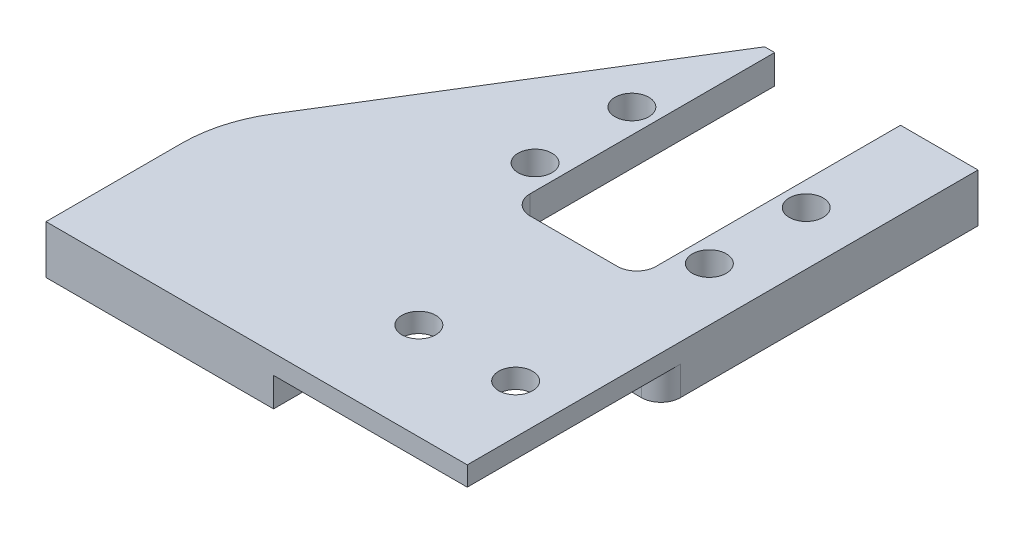
SolidWorks part; units mm, degrees
ref_plane "前视基准面" through (0, 0, 0) normal (0, 0, 1) x (1, 0, 0)
ref_plane "上视基准面" through (0, 0, 0) normal (0, 1, 0) x (1, 0, 0)
ref_plane "右视基准面" through (0, 0, 0) normal (1, 0, 0) x (0, 0, -1)
sketch "草图1" plane through (0, 0, 0) normal (0, 1, 0) x (1, 0, 0)
  line L1 (-17.5, -27.5) -> (17.5, -27.5)
  line L2 (-17.5, -27.5) -> (-17.5, 27.5)
  line L3 (-17.5, 27.5) -> (17.5, 27.5)
  line L4 (17.5, -27.5) -> (17.5, 27.5)
  line L5 (-17.5, -27.5) -> (17.5, 27.5) construction
  line L6 (-17.5, 27.5) -> (17.5, -27.5) construction
  point P0 (0, 0)
  dimension "D1" = 55
  dimension "D2" = 35
extrude "凸台-拉伸1" add sketch "草图1" along normal blind 1
sketch "草图2" plane through (0, 1, 0) normal (0, 1, 0) x (1, 0, 0)
  line L0 (-105.917, 0) -> (-62.25, 0) construction
  line L1 (106.75, 2.25) -> (121.75, 2.25)
  line L2 (-31.4474, 57.1013) -> (151.75, 26.6691)
  line L4 (124.0586, 2.6571) -> (154.0586, 13.5762)
  line L5 (-60.1618, 23.6059) -> (-42.6093, 52.0296)
  line L6 (121.75, 2.25) -> (121.75, 9) construction
  line L7 (121.75, -2.25) -> (121.75, -9) construction
  line L8 (-60.1618, -23.6059) -> (-42.6093, -52.0296)
  line L9 (124.0586, -2.6571) -> (154.0586, -13.5762)
  line L10 (121.75, -9) -> (128.5, -9)
  line L11 (-31.4474, -57.1013) -> (151.75, -26.6691)
  line L12 (106.75, -2.25) -> (121.75, -2.25)
  line L13 (-62.25, 16.25) -> (-62.25, -16.25)
  line L14 (106.75, 2.25) -> (106.75, -2.25)
  line L15 (106.75, 0) -> (124.0666, 0) construction
  arc A0 (-60.1618, 23.6059) -> (-62.25, 16.25) centre (-48.25, 16.25) ccw
  arc A1 (-31.4474, 57.1013) -> (-42.6093, 52.0296) centre (-33.25, 46.25) ccw
  arc A2 (121.75, 2.25) -> (124.0586, 2.6571) centre (121.75, 9) ccw
  arc A3 (154.0586, 13.5762) -> (151.75, 26.6691) centre (151.75, 19.9191) ccw
  arc A4 (154.0586, -13.5762) -> (151.75, -26.6691) centre (151.75, -19.9191) cw
  arc A5 (121.75, -2.25) -> (128.5, -9) centre (121.75, -9) cw
  arc A6 (-31.4474, -57.1013) -> (-42.6093, -52.0296) centre (-33.25, -46.25) cw
  arc A7 (-60.1618, -23.6059) -> (-62.25, -16.25) centre (-48.25, -16.25) cw
  line M10 (17.5, -27.5) -> (17.5, 27.5)
  line M11 (17.5, 27.5) -> (-17.5, 27.5)
  line M12 (-17.5, 27.5) -> (-17.5, -27.5)
  line M13 (-17.5, -27.5) -> (17.5, -27.5)
  dimension "D2" = 28
  dimension "D3" = 48.25
  dimension "D4" = 22
  dimension "D5" = 15
  dimension "D7" = 13.5
  dimension "D10" = 13.5
  dimension "D11" = 30
  dimension "D1" = 2.25
  dimension "D8" = 20
  dimension "D9" = 30
  dimension "D12" = 15
extrude "凸台-拉伸2" add sketch "草图2" along normal blind 3 contours A7 L8 A6 L11 A4 L9 A5 L12 L14 L1 A2 L4 A3 L2 A1 L5 A0 L13 | M13 M10 M11 M12 region at (37.3678, 1, 0) region at (0, 1, 0)
sketch "草图3" plane through (0, 4, 0) normal (0, 1, 0) x (1, 0, 0)
  circle A0 centre (-48.25, 16.25) radius 5
  circle A1 centre (-48.25, -16.25) radius 5
  circle A2 centre (-33.25, 46.25) radius 6.6982
  circle A3 centre (151.75, 19.9191) radius 2.5794
  circle A4 centre (121.75, 9) radius 2.5794
  circle A5 centre (121.75, -9) radius 2.5794
  circle A6 centre (151.75, -19.9191) radius 2.5794
  circle A7 centre (-33.25, -46.25) radius 6.6982
  dimension "D1" = 10
extrude "切除-拉伸1" cut sketch "草图3" against normal through all contours A0 | A1 region at (-48.25, 4, -16.25)
sketch "草图4" plane through (0, 4, 0) normal (0, 1, 0) x (1, 0, 0)
  circle A0 centre (-33.25, 46.25) radius 4
  circle A1 centre (-33.25, -46.25) radius 4
  dimension "D1" = 8
  dimension "D2" = 8
extrude "切除-拉伸2" cut sketch "草图4" against normal blind 2
sketch "草图5" plane through (0, 4, 0) normal (0, 1, 0) x (1, 0, 0)
  circle A0 centre (121.75, 9) radius 2
  circle A1 centre (121.75, -9) radius 2
  circle A2 centre (151.75, 19.9191) radius 2
  circle A3 centre (151.75, -19.9191) radius 2
  dimension "D1" = 4
extrude "切除-拉伸3" cut sketch "草图5" against normal blind 2
sketch "草图8" plane through (0, 1, 0) normal (0, -1, 0) x (1, 0, 0)
  line L1 (-39.75, -26.25) -> (-26.75, -26.25)
  line L2 (-39.75, -26.25) -> (-39.75, -66.25)
  line L3 (-39.75, -66.25) -> (-26.75, -66.25)
  line L4 (-26.75, -26.25) -> (-26.75, -66.25)
  line L5 (-39.75, -26.25) -> (-26.75, -66.25) construction
  line L6 (-39.75, -66.25) -> (-26.75, -26.25) construction
  line L16 (124.0586, 2.6571) -> (154.0586, 13.5762)
  line L17 (151.75, 26.6691) -> (-31.4474, 57.1013)
  line L18 (-42.6093, 52.0296) -> (-60.1618, 23.6059)
  line L19 (-62.25, 16.25) -> (-62.25, -16.25)
  line L20 (-60.1618, -23.6059) -> (-42.6093, -52.0296)
  line L21 (-31.4474, -57.1013) -> (151.75, -26.6691)
  line L22 (154.0586, -13.5762) -> (124.0586, -2.6571)
  line L23 (121.75, -2.25) -> (106.75, -2.25)
  line L24 (106.75, -2.25) -> (106.75, 2.25)
  line L25 (106.75, 2.25) -> (121.75, 2.25)
  line L26 (124.0586, 2.6571) -> (154.0586, 13.5762)
  line L27 (151.75, 26.6691) -> (-31.4474, 57.1013)
  line L28 (-42.6093, 52.0296) -> (-60.1618, 23.6059)
  line L31 (-31.4474, -57.1013) -> (151.75, -26.6691)
  line L32 (154.0586, -13.5762) -> (124.0586, -2.6571)
  line L33 (121.75, -2.25) -> (106.75, -2.25)
  line L34 (106.75, -2.25) -> (106.75, 2.25)
  line L35 (106.75, 2.25) -> (121.75, 2.25)
  arc A8 (154.0586, 13.5762) -> (151.75, 26.6691) centre (151.75, 19.9191) ccw
  arc A9 (-31.4474, 57.1013) -> (-42.6093, 52.0296) centre (-33.25, 46.25) ccw
  arc A10 (-60.1618, 23.6059) -> (-62.25, 16.25) centre (-48.25, 16.25) ccw
  arc A11 (-62.25, -16.25) -> (-60.1618, -23.6059) centre (-48.25, -16.25) ccw
  arc A12 (-42.6093, -52.0296) -> (-31.4474, -57.1013) centre (-33.25, -46.25) ccw
  arc A13 (151.75, -26.6691) -> (154.0586, -13.5762) centre (151.75, -19.9191) ccw
  arc A14 (124.0586, -2.6571) -> (121.75, -2.25) centre (121.75, -9) ccw
  arc A15 (121.75, 2.25) -> (124.0586, 2.6571) centre (121.75, 9) ccw
  arc A16 (154.0586, 13.5762) -> (151.75, 26.6691) centre (151.75, 19.9191) ccw
  arc A17 (-31.4474, 57.1013) -> (-42.6093, 52.0296) centre (-33.25, 46.25) ccw
  arc A18 (-60.1618, 23.6059) -> (-62.25, 16.25) centre (-48.25, 16.25) ccw
  arc A19 (-62.25, -16.25) -> (-60.1618, -23.6059) centre (-48.25, -16.25) ccw
  arc A20 (-42.6093, -52.0296) -> (-31.4474, -57.1013) centre (-33.25, -46.25) ccw
  arc A21 (151.75, -26.6691) -> (154.0586, -13.5762) centre (151.75, -19.9191) ccw
  arc A22 (124.0586, -2.6571) -> (121.75, -2.25) centre (121.75, -9) ccw
  arc A23 (121.75, 2.25) -> (124.0586, 2.6571) centre (121.75, 9) ccw
  point P0 (-33.25, -46.25)
  arc M32 (-42.6093, -52.0296) -> (-31.4474, -57.1013) centre (-33.25, -46.25) ccw
  line M33 (-31.4474, -57.1013) -> (151.75, -26.6691)
  dimension "D1" = 13
  dimension "D2" = 40
  dimension "D3" = 0
extrude "凸台-拉伸3" add sketch "草图8" along normal blind 7 contours L4 L1 L2 M32 M33 region at (-33.2258, 1, -41.4837)
mirror "镜向1" about plane through (0, 0, 0) normal (0, 0, 1) of "凸台-拉伸3"
sketch "草图9" plane through (0, -6, 0) normal (0, -1, 0) x (1, 0, 0)
  line L0 (-39.75, -26.25) -> (-26.75, -26.25) construction
  line L2 (-38.25, -53.75) -> (-38.25, -27.75)
  line L3 (-38.25, -27.75) -> (-28.25, -27.75)
  line L4 (-28.25, -53.75) -> (-28.25, -27.75)
  line L5 (-35.5448, -54.7408) -> (-28.25, -27.75) construction
  line L6 (-38.25, -27.75) -> (-31.223, -53.75) construction
  line L8 (-28.25, -53.75) -> (-38.25, -53.75)
  point P0 (-33.25, -46.25)
  dimension "D1" = 10
  dimension "D2" = 1.5
  dimension "D3" = 26
extrude "切除-拉伸4" cut sketch "草图9" against normal through all from offset 1.5 offset against normal yes
mirror "镜向2" about plane through (0, 0, 0) normal (0, 0, 1) of "切除-拉伸4"
sketch "草图10" plane through (0, 0, -53.75) normal (0, 0, 1) x (1, 0, 0)
  line L4 (-38.25, -4.5) -> (-28.25, -4.5)
  line L5 (-28.25, -4.5) -> (-28.25, 4)
  line L6 (-28.25, 4) -> (-38.25, 4)
  line L7 (-38.25, 4) -> (-38.25, -4.5)
  line L8 (-38.25, -4.5) -> (-28.25, -4.5)
  line L9 (-28.25, -4.5) -> (-28.25, 4)
  line L10 (-28.25, 4) -> (-38.25, 4)
  line L11 (-38.25, 4) -> (-38.25, -4.5)
  circle A0 centre (-33.25, -1.5) radius 1.5
  dimension "D2" = 3
  dimension "D3" = 3
  dimension "D1" = 0
extrude "切除-拉伸5" cut sketch "草图10" against normal through all contours A0 region at (-33.25, -1.5, -53.75)
mirror "镜向3" about plane through (0, 0, 0) normal (0, 0, 1) of "切除-拉伸5"
sketch "草图12" plane through (0, 4, 0) normal (0, 1, 0) x (1, 0, 0)
  line L3 (152.5362, 34.6481) -> (-30.1364, 64.9932)
  line L5 (-42.6093, 52.0296) -> (-60.1618, 23.6059) construction
  line L6 (124.0586, 2.6571) -> (154.0586, 13.5762) construction
  line L10 (154.0586, -13.5762) -> (124.0586, -2.6571)
  line L11 (121.75, -2.25) -> (106.75, -2.25)
  line L12 (106.75, -2.25) -> (106.75, 2.25)
  line L13 (106.75, 2.25) -> (121.75, 2.25)
  line L14 (124.0586, 2.6571) -> (154.0586, 13.5762)
  line L15 (151.75, 26.6691) -> (-31.4474, 57.1013)
  line L16 (-42.6093, 52.0296) -> (-60.1618, 23.6059)
  line L17 (-62.25, 16.25) -> (-62.25, -16.25)
  line L18 (-60.1618, -23.6059) -> (-42.6093, -52.0296)
  line L19 (-31.4474, -57.1013) -> (151.75, -26.6691)
  line L23 (-62.25, 2.25) -> (121.75, 2.25)
  line L24 (124.0586, 2.6571) -> (166.3826, 18.0617)
  line L26 (-34.4695, 65.2108) -> (-60.1618, 23.6059)
  line L27 (-62.25, 16.25) -> (-62.25, 2.25)
  line L30 (-49.416, 56.233) -> (-66.9685, 27.8093) construction
  line L31 (-70.25, 16.25) -> (-70.25, -5.75) construction
  line L32 (-70.25, -5.75) -> (121.75, -5.75) construction
  line L33 (126.7948, -4.8605) -> (156.7948, 6.0586) construction
  line L34 (151.75, 26.6691) -> (-31.4474, 57.1013) construction
  arc A1 (166.3826, 18.0617) -> (152.5362, 34.6481) centre (151.75, 19.9191) ccw
  arc A2 (-30.1364, 64.9932) -> (-34.4695, 65.2108) centre (-33.25, 46.25) ccw
  arc A4 (-30.1364, 64.9932) -> (-49.416, 56.233) centre (-33.25, 46.25) ccw construction
  arc A5 (156.7948, 6.0586) -> (152.5362, 34.6481) centre (151.75, 19.9191) ccw construction
  arc A8 (124.0586, -2.6571) -> (121.75, -2.25) centre (121.75, -9) ccw
  arc A9 (121.75, 2.25) -> (124.0586, 2.6571) centre (121.75, 9) ccw
  arc A10 (154.0586, 13.5762) -> (151.75, 26.6691) centre (151.75, 19.9191) ccw
  arc A11 (-31.4474, 57.1013) -> (-42.6093, 52.0296) centre (-33.25, 46.25) ccw
  arc A12 (-60.1618, 23.6059) -> (-62.25, 16.25) centre (-48.25, 16.25) ccw
  arc A13 (-62.25, -16.25) -> (-60.1618, -23.6059) centre (-48.25, -16.25) ccw
  arc A14 (-42.6093, -52.0296) -> (-31.4474, -57.1013) centre (-33.25, -46.25) ccw
  arc A15 (151.75, -26.6691) -> (154.0586, -13.5762) centre (151.75, -19.9191) ccw
  arc A17 (121.75, 2.25) -> (124.0586, 2.6571) centre (121.75, 9) ccw
  arc A20 (-60.1618, 23.6059) -> (-62.25, 16.25) centre (-48.25, 16.25) ccw
  arc A24 (-66.9685, 27.8093) -> (-70.25, 16.25) centre (-48.25, 16.25) ccw construction
  arc A25 (121.75, -5.75) -> (126.7948, -4.8605) centre (121.75, 9) ccw construction
  arc A26 (-31.4474, 57.1013) -> (-42.6093, 52.0296) centre (-33.25, 46.25) ccw construction
  arc A27 (154.0586, 13.5762) -> (151.75, 26.6691) centre (151.75, 19.9191) ccw construction
  dimension "D1" = 0
  dimension "D2" = 8
extrude "凸台-拉伸4" add sketch "草图12" along normal blind 3
sketch "草图13" plane through (0, 4, 0) normal (0, -1, 0) x (1, 0, 0)
  line L1 (-119.1699, 86.8947) -> (214.8426, 86.8947)
  line L2 (-119.1699, 86.8947) -> (-119.1699, -74.5615)
  line L3 (-119.1699, -74.5615) -> (214.8426, -74.5615)
  line L4 (214.8426, 86.8947) -> (214.8426, -74.5615)
  line L5 (-119.1699, 86.8947) -> (214.8426, -74.5615) construction
  line L6 (-119.1699, -74.5615) -> (214.8426, 86.8947) construction
  point P0 (47.8363, 6.1666)
extrude "切除-拉伸6" cut sketch "草图13" along normal blind 10
sketch "草图14" plane through (0, 4, 0) normal (0, -1, 0) x (1, 0, 0)
  circle A0 centre (151.75, -19.9191) radius 3.5
  circle A1 centre (121.75, -9) radius 3.5
  dimension "D2" = 7
  dimension "D3" = 7
extrude "切除-拉伸7" cut sketch "草图14" against normal blind 2.5
sketch "草图15" plane through (0, 4, 0) normal (0, -1, 0) x (1, 0, 0)
  circle A0 centre (-48.25, -16.25) radius 5
  dimension "D1" = 10
extrude "切除-拉伸8" cut sketch "草图15" against normal through all
sketch "草图17" plane through (0, 4, 0) normal (0, -1, 0) x (1, 0, 0)
  line L0 (-30.6281, -62.0337) -> (152.2188, -31.6598)
  line L1 (-34.4695, -65.2108) -> (-36.5044, -61.9155)
  line L3 (166.3826, -18.0617) -> (163.0963, -16.8656)
  line L5 (166.3826, -18.0617) -> (124.0586, -2.6571)
  line L6 (121.75, -2.25) -> (-62.25, -2.25)
  line L7 (-62.25, -2.25) -> (-62.25, -16.25)
  line L8 (-60.1618, -23.6059) -> (-34.4695, -65.2108)
  line L9 (-30.1364, -64.9932) -> (152.5362, -34.6481)
  line L14 (-30.1364, -64.9932) -> (152.5362, -34.6481)
  arc A0 (-36.5044, -61.9155) -> (-30.6281, -62.0337) centre (-33.25, -46.25) ccw
  arc A1 (152.2188, -31.6598) -> (163.0963, -16.8656) centre (151.75, -19.9191) ccw
  arc A2 (-34.2769, -62.217) -> (-30.6281, -62.0337) centre (-33.25, -46.25) ccw construction
  arc A3 (152.2188, -31.6598) -> (163.4065, -18.4395) centre (151.75, -19.9191) ccw construction
  arc A4 (124.0586, -2.6571) -> (121.75, -2.25) centre (121.75, -9) ccw
  arc A5 (-62.25, -16.25) -> (-60.1618, -23.6059) centre (-48.25, -16.25) ccw
  arc A6 (-34.4695, -65.2108) -> (-30.1364, -64.9932) centre (-33.25, -46.25) ccw
  arc A7 (152.5362, -34.6481) -> (166.3826, -18.0617) centre (151.75, -19.9191) ccw
  arc A10 (-34.4695, -65.2108) -> (-30.1364, -64.9932) centre (-33.25, -46.25) ccw
  arc A11 (152.5362, -34.6481) -> (166.3826, -18.0617) centre (151.75, -19.9191) ccw
  dimension "D1" = 0
  dimension "D2" = 3
extrude "凸台-拉伸5" add sketch "草图17" along normal blind 16
sketch "草图18" plane through (0, 7, 0) normal (0, 1, 0) x (1, 0, 0)
  line L1 (-39.75, 26.25) -> (-26.75, 26.25)
  line L2 (-39.75, 26.25) -> (-39.75, 56.6598)
  line L4 (-26.75, 26.25) -> (-26.75, 64.4306)
  line L5 (-39.75, 26.25) -> (-27.311, 64.5238) construction
  line L6 (-37.7079, 59.9667) -> (-26.75, 26.25) construction
  line L11 (-62.25, 16.25) -> (-62.25, 2.25)
  line L12 (-62.25, 2.25) -> (121.75, 2.25)
  line L13 (124.0586, 2.6571) -> (166.3826, 18.0617)
  line L14 (152.5362, 34.6481) -> (-30.1364, 64.9932)
  line L15 (-34.4695, 65.2108) -> (-60.1618, 23.6059)
  line L19 (-26.75, 64.4306) -> (-30.1364, 64.9932)
  line L20 (-34.4695, 65.2108) -> (-39.75, 56.6598)
  arc A0 (-30.1364, 64.9932) -> (-34.4695, 65.2108) centre (-33.25, 46.25) ccw construction
  arc A1 (-30.1364, 64.9932) -> (-34.4695, 65.2108) centre (-33.25, 46.25) ccw
  arc A6 (121.75, 2.25) -> (124.0586, 2.6571) centre (121.75, 9) ccw
  arc A7 (166.3826, 18.0617) -> (152.5362, 34.6481) centre (151.75, 19.9191) ccw
  arc A8 (-30.1364, 64.9932) -> (-34.4695, 65.2108) centre (-33.25, 46.25) ccw
  arc A9 (-60.1618, 23.6059) -> (-62.25, 16.25) centre (-48.25, 16.25) ccw
  arc A10 (121.75, 2.25) -> (124.0586, 2.6571) centre (121.75, 9) ccw
  arc A12 (-30.1364, 64.9932) -> (-34.4695, 65.2108) centre (-33.25, 46.25) ccw
  line M18 (152.5362, 34.6481) -> (-30.1364, 64.9932)
  arc M19 (-30.1364, 64.9932) -> (-34.4695, 65.2108) centre (-33.25, 46.25) ccw
  line M20 (-34.4695, 65.2108) -> (-60.1618, 23.6059)
  dimension "D3" = 0
extrude "凸台-拉伸6" add sketch "草图18" along normal blind 7 contours L1 L4 L2 M18 M19 M20 region at (-33.0469, 7, -44.8798)
sketch "草图19" plane through (0, 14, 0) normal (0, 1, 0) x (1, 0, 0)
  line L5 (-38.25, 53.75) -> (-28.25, 53.75)
  line L8 (-38.25, 27.75) -> (-28.25, 27.75)
  line L9 (-28.25, 64.75) -> (-28.25, 64.6798)
  line L10 (-39.75, 26.25) -> (-26.75, 26.25)
  line L11 (-26.75, 26.25) -> (-26.75, 64.4306)
  line L12 (-26.75, 64.4306) -> (-30.1364, 64.9932)
  line L13 (-34.4695, 65.2108) -> (-39.75, 56.6598)
  line L14 (-39.75, 56.6598) -> (-39.75, 26.25)
  line L17 (-26.75, 64.4306) -> (-28.6727, 64.75)
  line L18 (-34.4695, 65.2108) -> (-34.754, 64.75)
  line L21 (-38.25, 27.75) -> (-31.223, 53.75) construction
  line L22 (-38.25, 53.75) -> (-38.25, 27.75)
  line L23 (-35.277, 53.75) -> (-28.25, 27.75) construction
  line L24 (-28.2682, 64.6828) -> (-28.25, 64.75) construction
  line L25 (-28.25, 53.75) -> (-28.25, 27.75)
  line L27 (-28.6727, 64.75) -> (-28.25, 64.75)
  arc A2 (-30.1364, 64.9932) -> (-34.4695, 65.2108) centre (-33.25, 46.25) ccw
  dimension "D2" = 10
  dimension "D4" = 26
  dimension "D1" = 0
extrude "切除-拉伸9" cut sketch "草图19" against normal through all from offset 1.5 contours L25 L5 L22 L8 region at (-33.25, 14, -40.75) offset against normal yes
sketch "草图20" plane through (0, 0, -53.75) normal (0, 0, 1) x (1, 0, 0)
  line L4 (-38.25, 4) -> (-28.25, 4)
  line L5 (-28.25, 4) -> (-28.25, 12.5)
  line L6 (-28.25, 12.5) -> (-38.25, 12.5)
  line L7 (-38.25, 12.5) -> (-38.25, 4)
  line L8 (-38.25, 4) -> (-28.25, 4)
  line L9 (-28.25, 4) -> (-28.25, 12.5)
  line L10 (-28.25, 12.5) -> (-38.25, 12.5)
  line L11 (-38.25, 12.5) -> (-38.25, 4)
  circle A0 centre (-33.25, 9.5) radius 1.5
  dimension "D2" = 3
  dimension "D3" = 3
  dimension "D1" = 0
extrude "切除-拉伸10" cut sketch "草图20" against normal through all contours A0 region at (-33.25, 9.5, -53.75)
thread "螺纹线1" pitch 0.6 method cut profile "螺纹线轮廓1" start angle 0, offset 0, length 15, pitch 0.6, diameter 3
ref_plane "基准面1" through (-34.75, 9.5, -53.75) normal (0, -1, 0) x (-1, 0, 0)
sketch "螺纹线轮廓1" plane through (-34.75, 9.5, -53.75) normal (0, -1, 0) x (-1, 0, 0)
  line L0 (0, 0) -> (0, 0.6) construction
  line L1 (0, 0) -> (0.3248, 0.1875)
  line L2 (0.3248, 0.1875) -> (0.3248, 0.2625)
  line L3 (0.3248, 0.2625) -> (0, 0.45)
  line L4 (0.3248, 0.225) -> (0, 0.225) construction
  line L11 (0, 0) -> (0, 0.45)
  point P2 (0, 0)
  dimension "Pitch" = 0.6
  dimension "Profile_Angle" = 60
  dimension "Profile_Land" = 0.075
  dimension "Profile_Height" = 0.3248
sketch "草图21" plane through (0, 14, 0) normal (0, 1, 0) x (1, 0, 0)
  line L0 (-38.25, 27.75) -> (-28.25, 27.75) construction
  line L1 (-39.75, 27.75) -> (-26.75, 27.75)
  line L5 (-39.75, 26.25) -> (-26.75, 26.25)
  line L6 (-26.75, 26.25) -> (-26.75, 64.4306)
  line L7 (-26.75, 64.4306) -> (-30.1364, 64.9932)
  line L8 (-34.4695, 65.2108) -> (-39.75, 56.6598)
  line L9 (-39.75, 56.6598) -> (-39.75, 26.25)
  line L11 (-26.75, 27.75) -> (-26.75, 64.4306)
  line L12 (-26.75, 64.4306) -> (-30.1364, 64.9932)
  line L13 (-34.4695, 65.2108) -> (-39.75, 56.6598)
  line L14 (-39.75, 56.6598) -> (-39.75, 27.75)
  arc A1 (-30.1364, 64.9932) -> (-34.4695, 65.2108) centre (-33.25, 46.25) ccw
  arc A2 (-30.1364, 64.9932) -> (-34.4695, 65.2108) centre (-33.25, 46.25) ccw
  dimension "D1" = 0
extrude "切除-拉伸11" cut sketch "草图21" against normal through all
sketch "草图22" plane through (0, 14, 0) normal (0, 1, 0) x (1, 0, 0)
  line L4 (-26.75, 27.75) -> (-39.75, 27.75)
  line L5 (-39.75, 27.75) -> (-39.75, 26.25)
  line L6 (-39.75, 26.25) -> (-26.75, 26.25)
  line L7 (-26.75, 26.25) -> (-26.75, 27.75)
  line L8 (-26.75, 27.75) -> (-39.75, 27.75)
  line L9 (-39.75, 27.75) -> (-39.75, 26.25)
  line L10 (-39.75, 26.25) -> (-26.75, 26.25)
  line L11 (-26.75, 26.25) -> (-26.75, 27.75)
  dimension "D1" = 0
extrude "切除-拉伸12" cut sketch "草图22" against normal up to surface (7 mm away) up to face at (-48.25, 7, -21.25)
sketch "草图23" plane through (0, 7, 0) normal (0, 1, 0) x (1, 0, 0)
  line L0 (-45.75, 27.75) -> (-20.75, 27.75)
  line L1 (-20.75, 27.75) -> (-18.75, 27.75)
  line L2 (-18.75, 63.1017) -> (-18.75, 2.25)
  line L8 (-26.75, 64.4306) -> (-26.75, 27.75)
  line L9 (-26.75, 27.75) -> (-39.75, 27.75)
  line L10 (-39.75, 27.75) -> (-39.75, 56.6598)
  line L11 (-39.75, 56.6598) -> (-60.1618, 23.6059)
  line L12 (-62.25, 16.25) -> (-62.25, 2.25)
  line L13 (-62.25, 2.25) -> (121.75, 2.25)
  line L14 (124.0586, 2.6571) -> (166.3826, 18.0617)
  line L15 (152.5362, 34.6481) -> (-26.75, 64.4306)
  line L16 (-26.75, 64.4306) -> (-26.75, 27.75)
  line L17 (-26.75, 27.75) -> (-39.75, 27.75)
  line L18 (-39.75, 27.75) -> (-39.75, 56.6598)
  line L19 (-39.75, 56.6598) -> (-60.1618, 23.6059)
  line L20 (-62.25, 16.25) -> (-62.25, 2.25)
  line L21 (-62.25, 2.25) -> (-18.75, 2.25)
  line L23 (-18.75, 63.1017) -> (-26.75, 64.4306)
  circle A0 centre (-48.25, 16.25) radius 5 construction
  circle A1 centre (-48.25, 16.25) radius 5
  arc A3 (-60.1618, 23.6059) -> (-62.25, 16.25) centre (-48.25, 16.25) ccw
  arc A4 (121.75, 2.25) -> (124.0586, 2.6571) centre (121.75, 9) ccw
  arc A5 (166.3826, 18.0617) -> (152.5362, 34.6481) centre (151.75, 19.9191) ccw
  arc A6 (-60.1618, 23.6059) -> (-62.25, 16.25) centre (-48.25, 16.25) ccw
  point P13 (-33.25, 27.75)
  line M14 (-26.75, 64.4306) -> (-26.75, 27.75)
  line M15 (-26.75, 27.75) -> (-39.75, 27.75)
  line M16 (-39.75, 27.75) -> (-39.75, 56.6598)
  line M17 (-39.75, 56.6598) -> (-60.1618, 23.6059)
  arc M18 (-60.1618, 23.6059) -> (-62.25, 16.25) centre (-48.25, 16.25) ccw
  line M19 (-62.25, 16.25) -> (-62.25, 2.25)
  line M20 (-62.25, 2.25) -> (121.75, 2.25)
  line M24 (152.5362, 34.6481) -> (-26.75, 64.4306)
  circle M25 centre (-48.25, 16.25) radius 5
  dimension "D2" = 25
  dimension "D3" = 2
  dimension "D1" = 0
extrude "凸台-拉伸7" add sketch "草图23" along normal blind 2 contours L2 L1 L0 M15 M16 M17 M18 M19 M20 M25 | L2 L0 L1 M24 M14 region at (-40.7754, 7, -19.3253) region at (-22.7746, 7, -45.7601)
sketch "草图24" plane through (0, 9, 0) normal (0, 1, 0) x (1, 0, 0)
  line L0 (-45.75, 27.75) -> (-20.75, 27.75)
  line L1 (-45.75, 27.75) -> (-45.75, 46.9437)
  line L2 (-39.75, 56.6598) -> (-60.1618, 23.6059) construction
  line L3 (-20.75, 27.75) -> (-20.75, 86.4202)
  line L4 (-20.75, 86.4202) -> (-45.75, 86.4202)
  line L5 (-45.75, 86.4202) -> (-45.75, 46.0349)
  point P3 (-33.25, 27.75)
  line M3 (-39.75, 27.75) -> (-39.75, 56.6598)
  line M4 (-39.75, 56.6598) -> (-60.1618, 23.6059)
  line M9 (-18.75, 63.1017) -> (-26.75, 64.4306)
  line M10 (-26.75, 64.4306) -> (-26.75, 27.75)
  dimension "D1" = 25
extrude "切除-拉伸15" cut sketch "草图24" against normal through all from offset 3 contours L1 L0 M3 M4 | L0 L3 M9 M10 region at (-42.548, 9, -39.9394) region at (-23.7638, 9, -45.8423) offset against normal yes
sketch "草图25" plane through (0, 4, 0) normal (0, -1, 0) x (1, 0, 0)
  circle A0 centre (-48.25, -16.25) radius 7
  dimension "D1" = 14
extrude "切除-拉伸16" cut sketch "草图25" against normal blind 4
sketch "草图26" plane through (0, 7, 0) normal (0, 1, 0) x (1, 0, 0)
  line L0 (-48.25, 16.25) -> (51.3855, 16.25)
  line L1 (1.75, 16.25) -> (5.75, 16.25) construction
  line L2 (1.75, 18) -> (5.75, 18)
  line L3 (1.75, 14.5) -> (5.75, 14.5)
  line L4 (41.75, 16.25) -> (45.75, 16.25) construction
  line L5 (41.75, 18) -> (45.75, 18)
  line L6 (41.75, 14.5) -> (45.75, 14.5)
  line L7 (81.75, 16.25) -> (85.75, 16.25) construction
  line L8 (81.75, 18) -> (85.75, 18)
  line L9 (81.75, 14.5) -> (85.75, 14.5)
  line L10 (1.75, 31.25) -> (1.75, 35.25) construction
  line L11 (0, 31.25) -> (0, 35.25)
  line L12 (3.5, 31.25) -> (3.5, 35.25)
  arc A0 (1.75, 18) -> (1.75, 14.5) centre (1.75, 16.25) ccw
  arc A1 (5.75, 14.5) -> (5.75, 18) centre (5.75, 16.25) ccw
  arc A2 (41.75, 18) -> (41.75, 14.5) centre (41.75, 16.25) ccw
  arc A3 (45.75, 14.5) -> (45.75, 18) centre (45.75, 16.25) ccw
  arc A4 (81.75, 18) -> (81.75, 14.5) centre (81.75, 16.25) ccw
  arc A5 (85.75, 14.5) -> (85.75, 18) centre (85.75, 16.25) ccw
  arc A6 (0, 31.25) -> (3.5, 31.25) centre (1.75, 31.25) ccw
  arc A7 (3.5, 35.25) -> (0, 35.25) centre (1.75, 35.25) ccw
  point P5 (3.75, 16.25)
  point P10 (43.75, 16.25)
  point P17 (83.75, 16.25)
  point P24 (3.75, 14.5)
  point P27 (1.75, 33.25)
  dimension "D1" = 3.5
  dimension "D2" = 4
  dimension "D3" = 40
  dimension "D4" = 40
  dimension "D5" = 50
  dimension "D6" = 15
extrude "切除-拉伸17" cut sketch "草图26" against normal blind 10 contours L12 A7 L11 A6 | L0 A3 L5 A2 | L6 A3 L0 A2 | L9 A5 L8 A4 | L2 A1 L3 A0 region at (43.75, 7, -17.0711) region at (43.75, 7, -15.4289) region at (83.75, 7, -16.25) region at (1.75, 7, -33.25)
sketch "草图27" plane through (0, 6, 0) normal (0, -1, 0) x (1, 0, 0)
  line L0 (-26.75, -27.75) -> (-20.75, -27.75)
  line L1 (-45.75, -27.75) -> (-39.75, -27.75)
  line L2 (-45.75, -27.75) -> (-39.75, -27.75) construction
  line L3 (-33.25, -27.75) -> (-33.25, -46.4587) construction
  line L4 (-45.75, -27.75) -> (-20.75, -27.75) construction
  circle A0 centre (-24.25, -32.75) radius 1.75
  circle A1 centre (-24.25, -42.75) radius 1.75
  circle A2 centre (-42.25, -32.75) radius 1.75
  circle A3 centre (-42.25, -42.75) radius 1.75
  dimension "D1" = 3.5
  dimension "D4" = 10
  dimension "D5" = 10
  dimension "D6" = 18
  dimension "D7" = 9
  dimension "D2" = 5
  dimension "D3" = 5
extrude "切除-拉伸18" cut sketch "草图27" against normal blind 10 contours A2 | A3 | A0 | A1 region at (-24.25, 6, -32.75) region at (-42.25, 6, -32.75) region at (-42.25, 6, -42.75)
sketch "草图28" plane through (0, -12, 0) normal (0, -1, 0) x (1, 0, 0)
  line L0 (-26.75, -64.4306) -> (-26.75, -27.75) construction
  line L1 (-26.75, -64.4306) -> (-26.75, -27.75)
  line L4 (-20.75, -60.3928) -> (-20.75, -63.4339)
  line L5 (-20.75, -63.4339) -> (152.5362, -34.6481)
  line L6 (166.3826, -18.0617) -> (163.0963, -16.8656)
  line L7 (152.2188, -31.6598) -> (-20.75, -60.3928)
  line L8 (-20.75, -60.3928) -> (-20.75, -63.4339)
  line L9 (-26.75, -64.4306) -> (152.5362, -34.6481)
  line L10 (166.3826, -18.0617) -> (163.0963, -16.8656)
  line L11 (152.2188, -31.6598) -> (-26.75, -61.3895)
  arc A2 (152.5362, -34.6481) -> (166.3826, -18.0617) centre (151.75, -19.9191) ccw
  arc A3 (152.2188, -31.6598) -> (163.0963, -16.8656) centre (151.75, -19.9191) ccw
  arc A4 (152.5362, -34.6481) -> (166.3826, -18.0617) centre (151.75, -19.9191) ccw
  arc A5 (152.2188, -31.6598) -> (163.0963, -16.8656) centre (151.75, -19.9191) ccw
  line M7 (-20.75, -60.3928) -> (-20.75, -63.4339)
  line M8 (-20.75, -63.4339) -> (152.5362, -34.6481)
  arc M9 (152.5362, -34.6481) -> (166.3826, -18.0617) centre (151.75, -19.9191) ccw
  line M10 (166.3826, -18.0617) -> (163.0963, -16.8656)
  arc M11 (163.0963, -16.8656) -> (152.2188, -31.6598) centre (151.75, -19.9191) cw
  line M12 (152.2188, -31.6598) -> (-20.75, -60.3928)
  dimension "D1" = 0
extrude "切除-拉伸19" cut sketch "草图28" against normal blind 60 and the other way through all contours M12 M7 M8 M9 M10 M11 | L11 L1 L9 M7 region at (-23.75, -12, -62.4117) region at (76.6873, -12, -45.2095)
sketch "草图29" plane through (0, 4, 0) normal (0, -1, 0) x (1, 0, 0)
  line L0 (152.2188, -31.6598) -> (-20.75, -60.3928) construction
  line L1 (152.2188, -31.6598) -> (-20.75, -60.3928)
  line L2 (151.75, -26.6691) -> (-21.5694, -55.4604)
  line L3 (124.0586, -2.6571) -> (163.0963, -16.8656) construction
  line L4 (124.0586, -2.6571) -> (163.0963, -16.8656)
  line L5 (-18.75, -60.0606) -> (-18.75, -2.25) construction
  line L6 (-18.75, -60.0606) -> (-18.75, -2.25)
  arc A0 (152.2188, -31.6598) -> (163.0963, -16.8656) centre (151.75, -19.9191) ccw construction
  arc A1 (152.2188, -31.6598) -> (163.0963, -16.8656) centre (151.75, -19.9191) ccw
  arc A2 (151.75, -26.6691) -> (154.0586, -13.5762) centre (151.75, -19.9191) ccw
  arc A3 (151.75, -26.6691) -> (158.2681, -18.165) centre (151.75, -19.9191) ccw construction
  arc M30 (152.2188, -31.6598) -> (163.0963, -16.8656) centre (151.75, -19.9191) ccw
  line M31 (163.0963, -16.8656) -> (124.0586, -2.6571)
  dimension "D1" = 5
extrude "切除-拉伸20" cut sketch "草图29" along normal blind 2 from surface contours A2 L2 L6 L1 M30 M31 region at (75.6352, 4, -41.4349) starting at face at (1.75, 7, -33.25)
sketch "草图30" plane through (-18.75, 0, 0) normal (1, 0, 0) x (0, 0, -1)
  line L1 (54.992, 5) -> (66.6455, 5)
  line L2 (54.992, 5) -> (54.992, 12.2878)
  line L3 (54.992, 12.2878) -> (66.6455, 12.2878)
  line L4 (66.6455, 5) -> (66.6455, 12.2878)
extrude "切除-拉伸21" cut sketch "草图30" against normal through all
sketch "草图31" plane through (0, 5, 0) normal (0, 1, 0) x (1, 0, 0)
  line L1 (-18.75, 54.992) -> (-22.5019, 54.992)
  line L2 (-18.75, 54.992) -> (-18.75, 61.757)
  line L3 (-18.75, 61.757) -> (-22.5019, 61.757)
  line L4 (-22.5019, 54.992) -> (-22.5019, 61.757)
extrude "切除-拉伸22" cut sketch "草图31" against normal blind 10
sketch "草图32" plane through (0, 5, 0) normal (0, 1, 0) x (1, 0, 0)
  line L1 (-18.75, 54.992) -> (-18.75, 60.0606) construction
  line L2 (-18.3403, 57.4582) -> (152.1597, 29.1353)
  line L3 (-18.75, 57.5263) -> (152.1597, 29.1353)
  line L4 (-18.75, 54.992) -> (-18.75, 60.0606) construction
  circle A0 centre (10.8863, 52.6032) radius 1 construction
  circle A1 centre (50.3456, 46.0484) radius 1
  circle A2 centre (89.8048, 39.4935) radius 1
  circle A3 centre (129.2641, 32.9387) radius 1
  circle A4 centre (10.8863, 52.6032) radius 1
  dimension "D2" = 2
  dimension "D4" = 40
  dimension "D5" = 40
  dimension "D6" = 40
  dimension "D3" = 29.6363
  dimension "D1" = 2.5
extrude "切除-拉伸23" cut sketch "草图32" against normal blind 10 contours L3 A4 | L3 A4 | L3 A1 | L3 A1 | A2 | A3 region at (10.9558, 5, -53.0219) region at (50.4151, 5, -46.467) region at (50.276, 5, -45.6297) region at (10.8167, 5, -52.1845)
sketch "草图33" plane through (0, 9, 0) normal (0, 1, 0) x (1, 0, 0)
  circle A0 centre (-48.25, 16.25) radius 6.5995
extrude "凸台-拉伸8" add sketch "草图33" against normal up to surface (1 mm away) up to face at (-48.25, 8, -23.25)
sketch "草图35" plane through (-18.75, 0, 0) normal (1, 0, 0) x (0, 0, -1)
  line L1 (-1.8703, 13.7705) -> (74.9556, 13.7705)
  line L2 (-1.8703, 13.7705) -> (-1.8703, -7.1415)
  line L3 (-1.8703, -7.1415) -> (74.9556, -7.1415)
  line L4 (74.9556, 13.7705) -> (74.9556, -7.1415)
extrude "切除-拉伸24" cut sketch "草图35" along normal through all
sketch "草图36" plane through (0, 4, 0) normal (0, -1, 0) x (1, 0, 0)
  line L1 (-18.75, -2.25) -> (-38.75, -2.25)
  line L2 (-18.75, -2.25) -> (-18.75, -22.25)
  line L3 (-18.75, -22.25) -> (-38.75, -22.25)
  line L4 (-38.75, -2.25) -> (-38.75, -22.25)
  dimension "D1" = 20
  dimension "D2" = 20
extrude "切除-拉伸25" cut sketch "草图36" against normal blind 3
sketch "草图37" plane through (0, 7, 0) normal (0, -1, 0) x (1, 0, 0)
  line L0 (-18.75, -12.25) -> (-35.8367, -12.25)
  line L1 (-18.75, -22.25) -> (-18.75, -2.25) construction
  circle A0 centre (-23.75, -12.25) radius 1.75
  circle A1 centre (-33.75, -12.25) radius 1.75
  dimension "D1" = 5
  dimension "D2" = 10
  dimension "D3" = 3.5
  dimension "D4" = 3.5
extrude "切除-拉伸26" cut sketch "草图37" against normal blind 10 contours L0 A0 | L0 A0 | A1 region at (-23.75, 7, -12.9927) region at (-23.75, 7, -11.5073)
fillet "圆角1" radius 2 6 edges at (-20.75, 5, -27.75) (-26.75, 7.5, -27.75) (-39.75, 7.5, -27.75) (-45.75, 5, -27.75) (-18.75, 5.5, -22.25) (-38.75, 5.5, -22.25)
